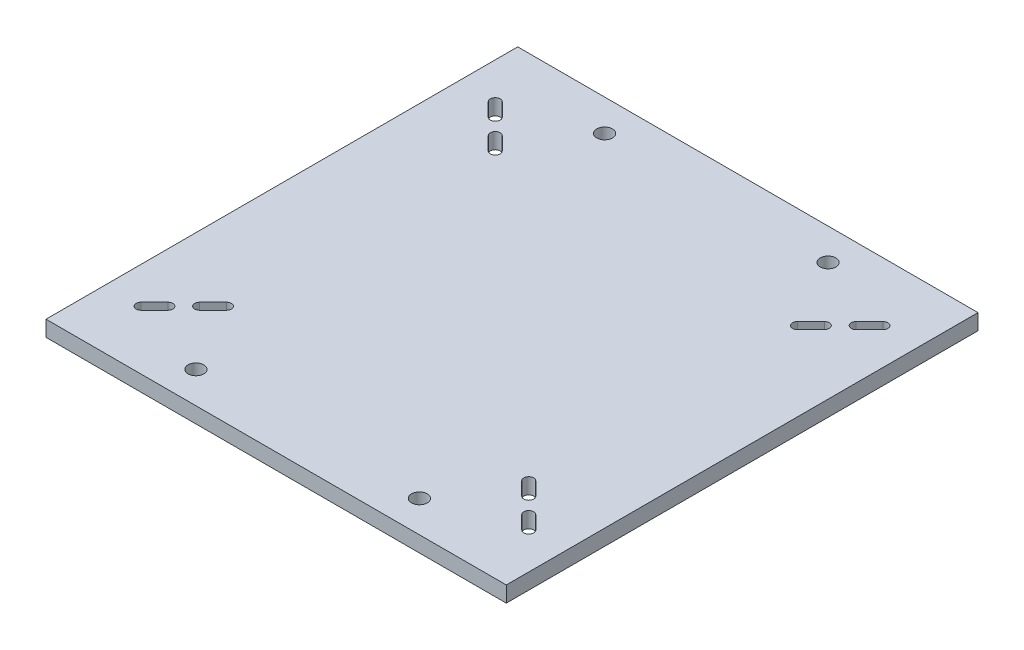
SolidWorks part; units mm, degrees
material "6061-T6 (SS)"
ref_plane "Front Plane" through (0, 0, 0) normal (0, 0, 1) x (1, 0, 0)
ref_plane "Top Plane" through (0, 0, 0) normal (0, 1, 0) x (1, 0, 0)
ref_plane "Right Plane" through (0, 0, 0) normal (1, 0, 0) x (0, 0, -1)
sketch "Sketch1" plane through (0, 0, 0) normal (0, 1, 0) x (1, 0, 0)
  line L1 (0, 0) -> (185.4, 0)
  line L2 (0, 0) -> (0, -190)
  line L3 (0, -190) -> (185.4, -190)
  line L4 (185.4, 0) -> (185.4, -190)
  dimension "D1" = 185.4
  dimension "D2" = 190
extrude "base plate" add sketch "Sketch1" against normal blind 6.35
sketch "center lines" plane through (0, 0, 0) normal (0, 1, 0) x (1, 0, 0)
  line L0 (92.7, 0) -> (92.7, -190) construction
  line L1 (185.4, 0) -> (0, 0) construction
  line L2 (0, -190) -> (185.4, -190) construction
  line L3 (0, -95) -> (185.4, -95) construction
  line L4 (0, 0) -> (0, -190) construction
  line L5 (185.4, -190) -> (185.4, 0) construction
sketch "Sketch3" plane through (0, 0, 0) normal (0, 1, 0) x (1, 0, 0)
  line L0 (1.825, -168.3487) -> (12.6013, -179.125)
  line L1 (12.6013, -179.125) -> (46.7263, -145)
  line L2 (46.7263, -145) -> (35.95, -134.2237)
  line L3 (35.95, -134.2237) -> (1.825, -168.3487)
  line L4 (14.6222, -166.3278) -> (20.0104, -160.9396) construction
  line L5 (13.208, -164.9135) -> (18.5962, -159.5254)
  line L6 (16.0365, -167.742) -> (21.4246, -162.3538)
  line L7 (0, -190) -> (185.4, -190) construction
  line L8 (31.8191, -149.1309) -> (26.4309, -154.5191) construction
  line L9 (33.2333, -150.5451) -> (27.8451, -155.9333)
  line L10 (92.7, 0) -> (92.7, -190) construction
  line L11 (0, -95) -> (185.4, -95) construction
  line L12 (46.7263, -45) -> (35.95, -55.7763)
  line L13 (12.6013, -10.875) -> (46.7263, -45)
  line L14 (1.825, -21.6513) -> (12.6013, -10.875)
  line L15 (35.95, -55.7763) -> (1.825, -21.6513)
  line L16 (172.7987, -10.875) -> (138.6737, -45)
  line L17 (183.575, -21.6513) -> (172.7987, -10.875)
  line L18 (149.45, -55.7763) -> (183.575, -21.6513)
  line L19 (138.6737, -45) -> (149.45, -55.7763)
  line L20 (138.6737, -145) -> (149.45, -134.2237)
  line L21 (172.7987, -179.125) -> (138.6737, -145)
  line L22 (183.575, -168.3487) -> (172.7987, -179.125)
  line L23 (149.45, -134.2237) -> (183.575, -168.3487)
  line L24 (30.4049, -147.7167) -> (25.0167, -153.1049)
  line L25 (14.6222, -23.6722) -> (20.0104, -29.0604) construction
  line L26 (13.208, -25.0865) -> (18.5962, -30.4746)
  line L27 (16.0365, -22.258) -> (21.4246, -27.6462)
  line L28 (31.8191, -40.8691) -> (26.4309, -35.4809) construction
  line L29 (33.2333, -39.4549) -> (27.8451, -34.0667)
  line L30 (30.4049, -42.2833) -> (25.0167, -36.8951)
  line L31 (170.7778, -23.6722) -> (165.3896, -29.0604) construction
  line L32 (172.192, -25.0865) -> (166.8038, -30.4746)
  line L33 (169.3635, -22.258) -> (163.9754, -27.6462)
  line L34 (153.5809, -40.8691) -> (158.9691, -35.4809) construction
  line L35 (152.1667, -39.4549) -> (157.5549, -34.0667)
  line L36 (154.9951, -42.2833) -> (160.3833, -36.8951)
  line L37 (153.5809, -149.1309) -> (158.9691, -154.5191) construction
  line L38 (152.1667, -150.5451) -> (157.5549, -155.9333)
  line L39 (154.9951, -147.7167) -> (160.3833, -153.1049)
  line L40 (170.7778, -166.3278) -> (165.3896, -160.9396) construction
  line L41 (172.192, -164.9135) -> (166.8038, -159.5254)
  line L42 (169.3635, -167.742) -> (163.9754, -162.3538)
  line L43 (35.95, -145) -> (35.95, -134.2237)
  line L44 (46.7263, -145) -> (35.95, -145)
  line L45 (35.95, -45) -> (35.95, -55.7763)
  line L46 (46.7263, -45) -> (35.95, -45)
  line L47 (149.45, -45) -> (149.45, -55.7763)
  line L48 (138.6737, -45) -> (149.45, -45)
  line L49 (149.45, -145) -> (149.45, -134.2237)
  line L50 (138.6737, -145) -> (149.45, -145)
  line L53 (185.4, 0) -> (0, 0) construction
  arc A0 (13.208, -164.9135) -> (16.0365, -167.742) centre (14.6222, -166.3278) ccw
  arc A1 (21.4246, -162.3538) -> (18.5962, -159.5254) centre (20.0104, -160.9396) ccw
  arc A2 (33.2333, -150.5451) -> (30.4049, -147.7167) centre (31.8191, -149.1309) ccw
  arc A3 (25.0167, -153.1049) -> (27.8451, -155.9333) centre (26.4309, -154.5191) ccw
  arc A4 (13.208, -25.0865) -> (16.0365, -22.258) centre (14.6222, -23.6722) cw
  arc A5 (21.4246, -27.6462) -> (18.5962, -30.4746) centre (20.0104, -29.0604) cw
  arc A6 (33.2333, -39.4549) -> (30.4049, -42.2833) centre (31.8191, -40.8691) cw
  arc A7 (25.0167, -36.8951) -> (27.8451, -34.0667) centre (26.4309, -35.4809) cw
  arc A8 (172.192, -25.0865) -> (169.3635, -22.258) centre (170.7778, -23.6722) ccw
  arc A9 (163.9754, -27.6462) -> (166.8038, -30.4746) centre (165.3896, -29.0604) ccw
  arc A10 (152.1667, -39.4549) -> (154.9951, -42.2833) centre (153.5809, -40.8691) ccw
  arc A11 (160.3833, -36.8951) -> (157.5549, -34.0667) centre (158.9691, -35.4809) ccw
  arc A12 (152.1667, -150.5451) -> (154.9951, -147.7167) centre (153.5809, -149.1309) cw
  arc A13 (160.3833, -153.1049) -> (157.5549, -155.9333) centre (158.9691, -154.5191) cw
  arc A14 (172.192, -164.9135) -> (169.3635, -167.742) centre (170.7778, -166.3278) cw
  arc A15 (163.9754, -162.3538) -> (166.8038, -159.5254) centre (165.3896, -160.9396) cw
  point P29 (17.3163, -163.6337)
  point P36 (29.125, -151.825)
  point P44 (17.3163, -26.3663)
  point P51 (29.125, -38.175)
  point P58 (168.0837, -26.3663)
  point P65 (156.275, -38.175)
  point P72 (156.275, -151.825)
  point P79 (168.0837, -163.6337)
  point P84 (21.4246, -159.5254)
  point P85 (25.0167, -155.9333)
  dimension "D6" = 2
  dimension "D10" = 5.08
  dimension "D9" = 5.842
  dimension "D1" = 48.26
  dimension "D2" = 15.24
  dimension "D3" = 45
  dimension "D4" = 100
  dimension "D5" = 113.5
  dimension "D7" = 7.62
  dimension "D8" = 7.62
extrude "slots" cut sketch "Sketch3" against normal through all contours A5 L27 A4 L26 | L33 A9 L32 A8 | L36 A11 L35 A10 | A13 L39 A12 L38 | A15 L42 A14 L41 | L6 A1 L5 A0 | L24 A3 L9 A2 | L30 A7 L29 A6 region at (17.3163, 0, 26.3663) region at (168.0837, 0, 26.3663) region at (156.275, 0, 38.175) region at (156.275, 0, 151.825) region at (168.0837, 0, 163.6337)
hole_wizard "Feet connection hole" positions "Sketch6" profile "Sketch7" hole size "1/4" standard "ANSI Inch" end condition through all
sketch "Sketch6" plane through (0, 0, 0) normal (0, 1, 0) x (1, 0, 0)
  line L0 (0, -190) -> (185.4, -190) construction
  line L3 (185.4, 0) -> (0, 0) construction
  line L4 (92.7, 0) -> (92.7, -190) construction
  point P3 (47.7, -177.3)
  point P19 (137.7, -12.7)
  point P33 (47.7, -12.7)
  point P37 (137.7, -177.3)
  dimension "D1" = 12.7
  dimension "D2" = 90
  dimension "D3" = 45
  dimension "D4" = 12.7
sketch "Sketch7" plane through (47.7, 0, 177.3) normal (1, 0, 0) x (0, 0, 1)
  line L0 (0, 0) -> (0, 6.35)
  line L1 (0, 6.35) -> (3.175, 6.35)
  line L2 (3.175, 6.35) -> (3.175, 0)
  line L5 (3.175, 0) -> (0, 0)
  line L11 (0, -6.35) -> (0, 107.95) construction
  dimension "Thru Hole Dia." = 6.35
  dimension "Thru Hole Depth" = 6.35
ref_plane "Center Plane" through (0, 0, 95) normal (0, 0, 1) x (1, 0, 0)
